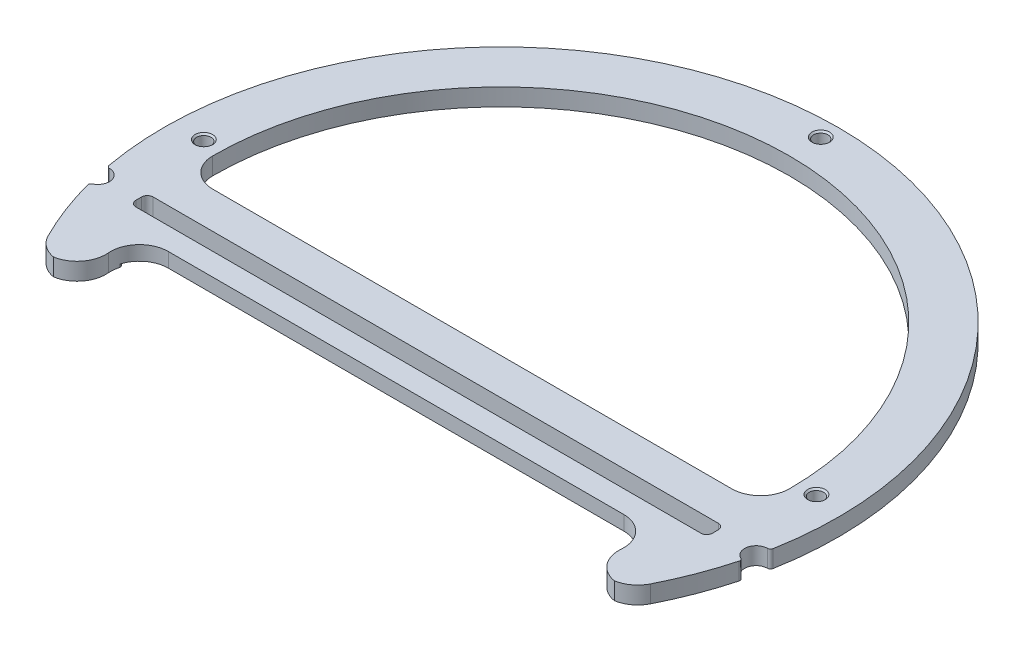
SolidWorks part; units mm, degrees
ref_plane "前视基准面" through (0, 0, 0) normal (0, 0, 1) x (1, 0, 0)
ref_plane "上视基准面" through (0, 0, 0) normal (0, 1, 0) x (1, 0, 0)
ref_plane "右视基准面" through (0, 0, 0) normal (1, 0, 0) x (0, 0, -1)
other "Configuration Table"
sketch "草图2" plane through (0, 0, 0) normal (0, 1, 0) x (1, 0, 0)
  circle A0 centre (0, 0) radius 58.5
  point P4 (-114.6944, 33.9154)
  dimension "D1" = 117
extrude "凸台-拉伸1" add sketch "草图2" along normal blind 3
sketch "草图3" plane through (0, 0, 0) normal (0, -1, 0) x (1, 0, 0)
  line L0 (-49.7494, 5) -> (49.7494, 5)
  arc A0 (-49.7494, 5) -> (49.7494, 5) centre (0, 0) ccw
  dimension "D1" = 100
  dimension "D2" = 5
extrude "切除-拉伸2" cut sketch "草图3" against normal through all
sketch "草图4" plane through (0, 0, 0) normal (0, -1, 0) x (-1, 0, 0)
  line L1 (-46.5639, -18.2154) -> (46.5639, -18.2154)
  arc A1 (-46.5639, -18.2154) -> (46.5639, -18.2154) centre (0, 0) ccw
  dimension "D1" = 100
extrude "切除-拉伸3" cut sketch "草图4" against normal through all
sketch "草图5" plane through (0, 0, 0) normal (0, 1, 0) x (1, 0, 0)
  line L1 (-53.5909, -87.9382) -> (53.5909, -87.9382)
  line L2 (-53.5909, -87.9382) -> (-53.5909, -29.0618)
  line L3 (-53.5909, -29.0618) -> (53.5909, -29.0618)
  line L4 (53.5909, -87.9382) -> (53.5909, -29.0618)
  line L5 (-53.5909, -87.9382) -> (53.5909, -29.0618) construction
  line L6 (-53.5909, -29.0618) -> (53.5909, -87.9382) construction
  circle A0 centre (0, 0) radius 58.5 construction
  point P0 (0, -58.5)
extrude "切除-拉伸8" cut sketch "草图5" along normal through all
fillet "圆角2" radius 5 4 edges at (-50.7707, 1.5, 29.0618) (-40.6868, 1.5, 29.0618) (50.7707, 1.5, 29.0618) (40.6868, 1.5, 29.0618)
sketch "草图6" plane through (0, 0, 0) normal (0, -1, 0) x (1, 0, 0)
  line L12 (-50, 13.34) -> (-50, 12.34)
  line L13 (-49, 11.34) -> (49, 11.34)
  line L14 (50, 12.34) -> (50, 13.34)
  line L24 (49, 14.34) -> (-49, 14.34)
  line L30 (-50, 13.34) -> (-50, 12.34)
  line L31 (-49, 11.34) -> (49, 11.34)
  line L32 (50, 12.34) -> (50, 13.34)
  line L33 (49, 14.34) -> (-49, 14.34)
  arc A4 (-50, 12.34) -> (-49, 11.34) centre (-49, 12.34) ccw
  arc A5 (49, 11.34) -> (50, 12.34) centre (49, 12.34) ccw
  arc A6 (50, 13.34) -> (49, 14.34) centre (49, 13.34) ccw
  arc A7 (-49, 14.34) -> (-50, 13.34) centre (-49, 13.34) ccw
  arc A12 (-50, 12.34) -> (-49, 11.34) centre (-49, 12.34) ccw
  arc A14 (49, 11.34) -> (50, 12.34) centre (49, 12.34) ccw
  arc A16 (50, 13.34) -> (49, 14.34) centre (49, 13.34) ccw
  arc A17 (-49, 14.34) -> (-50, 13.34) centre (-49, 13.34) ccw
  point P0 (-0.7773, 15.5362)
  dimension "D1" = 0
extrude "切除-拉伸9" cut sketch "草图6" against normal through all
fillet "圆角4" radius 5 2 edges at (49.7494, 1.5, 5) (-49.7494, 1.5, 5)
sketch "草图7" plane through (0, 0, 0) normal (0, -1, 0) x (1, 0, 0)
  line L1 (-42.6248, -22.2056) -> (42.6248, -22.2056)
  line L2 (-42.6248, -22.2056) -> (-42.6248, -27.2056)
  line L3 (-42.6248, -27.2056) -> (42.6248, -27.2056)
  line L4 (42.6248, -22.2056) -> (42.6248, -27.2056)
  line L5 (-42.6248, -22.2056) -> (42.6248, -27.2056) construction
  line L6 (-42.6248, -27.2056) -> (42.6248, -22.2056) construction
  point P0 (0, -24.7056)
  dimension "D1" = 5
fillet "圆角7" radius 5 2 edges at (46.5639, 1.5, 18.2154) (-46.5639, 1.5, 18.2154)
sketch "草图8" plane through (0, 0, 0) normal (0, -1, 0) x (1, 0, 0)
  line L0 (-49.7, 20.7467) -> (-49.7, 14.2873) construction
  line L1 (-49.7, 14.2873) -> (53.3, 14.2873) construction
  line L2 (53.3, 14.2873) -> (53.3, 20.7467) construction
  line L3 (53.3, 20.7467) -> (-49.7, 20.7467) construction
  line L4 (52, 21.2467) -> (-52, 21.2467)
  line L5 (-52, 21.2467) -> (-52, 13.7873)
  line L6 (-52, 13.7873) -> (52, 13.7873)
  line L7 (52, 13.7873) -> (52, 21.2467)
  point P10 (0, 13.7873)
extrude "切除-拉伸10" cut sketch "草图8" against normal blind 0.5
fillet "圆角8" radius 0.5 7 edges at (52, 0.25, 13.7873) (52, 0.25, 21.2467) (44.0894, 0.25, 21.2467) (-44.0894, 0.25, 21.2467) (-52, 0.25, 21.2467) (49.8944, 0.25, 13.7873) (-49.8944, 0.25, 13.7873)
sketch "草图9" plane through (0, 3, 0) normal (0, 1, 0) x (1, 0, 0)
  circle A0 centre (57.0735, -12.84) radius 2
  arc A1 (52.2495, -26.3105) -> (-52.2495, -26.3105) centre (0, 0) ccw construction
  circle A2 centre (-57.0735, -12.84) radius 2
  arc A3 (52.2495, -26.3105) -> (-52.2495, -26.3105) centre (0, 0) ccw construction
  dimension "D1" = 4
  dimension "D2" = 4
extrude "切除-拉伸11" cut sketch "草图9" against normal blind 10
fillet "圆角9" radius 0.5 4 edges at (-56.6012, 1.5, 14.7834) (-57.4791, 1.5, 10.8816) (56.6012, 1.5, 14.7834) (57.4791, 1.5, 10.8816)
sketch "草图10" plane through (0, 3, 0) normal (0, 1, 0) x (1, 0, 0)
  point P0 (53.2134, 1.4753)
  point P1 (-53.2134, 1.6686)
  point P3 (-0.0866, 55.5261)
  point P5 (68.8468, 52.778)
hole_wizard "M3 螺纹孔1" positions "草图10" profile "草图11" tap size "M3" standard "GB"
sketch "草图11" plane through (53.2134, 3, -1.4753) normal (1, 0, 0) x (0, 0, 1)
  line L0 (0, 0) -> (0, 4.6511)
  line L1 (0, 4.6511) -> (1.25, 3.9)
  line L2 (1.25, 3.9) -> (1.25, 0.275)
  line L3 (1.25, 0.275) -> (1.525, 0)
  line L5 (1.525, 0) -> (0, 0)
  line L6 (-1.25, 0.275) -> (-1.525, 0) construction
  line L10 (0, 4.6511) -> (-1.25, 3.9) construction
  line L11 (0, -6.35) -> (0, 107.95) construction
  dimension "螺纹孔钻头直径" = 2.5
  dimension "螺纹孔钻头深度" = 3.9
  dimension "近端锥形沉头孔直径" = 3.05
  dimension "近端锥形沉头孔角度" = 90
  dimension "导头角度" = 118
cosmetic thread "孔螺蚊线1" parameters "D1"=2.4, "D2"=3
cosmetic thread "孔螺蚊线2" parameters "D1"=2.4, "D2"=3
cosmetic thread "孔螺蚊线3" parameters "D1"=2.4, "D2"=3
